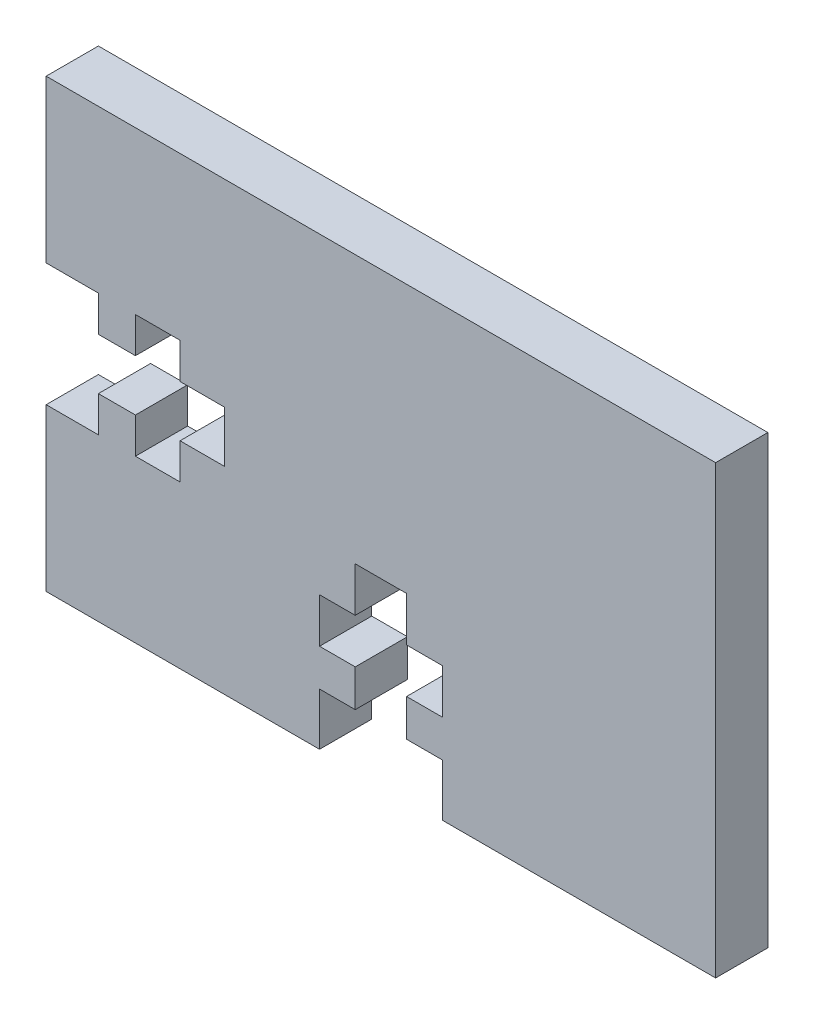
SolidWorks part; units mm, degrees
ref_plane "Front Plane" through (0, 0, 0) normal (0, 0, 1) x (1, 0, 0)
ref_plane "Top Plane" through (0, 0, 0) normal (0, 1, 0) x (1, 0, 0)
ref_plane "Right Plane" through (0, 0, 0) normal (1, 0, 0) x (0, 0, -1)
sketch "Sketch1" plane through (0, 0, 0) normal (0, 0, 1) x (1, 0, 0)
  line L0 (5.08, 14.1605) -> (2.9718, 14.1605)
  line L1 (0, 0) -> (38.1, 0)
  line L2 (0, 0) -> (0, 25.4)
  line L3 (0, 25.4) -> (38.1, 25.4)
  line L4 (38.1, 0) -> (38.1, 25.4)
  line L5 (5.08, 11.2395) -> (5.08, 9.2075)
  line L6 (5.08, 11.2395) -> (2.9718, 11.2395)
  line L7 (5.08, 14.1605) -> (5.08, 16.1925)
  line L8 (5.08, 16.1925) -> (7.62, 16.1925)
  line L9 (7.62, 16.1925) -> (7.62, 14.1605)
  line L10 (7.62, 14.1605) -> (10.16, 14.1605)
  line L11 (0, 12.7) -> (38.1, 12.7) construction
  line L12 (10.16, 14.1605) -> (10.16, 11.2395)
  line L13 (5.08, 9.2075) -> (7.62, 9.2075)
  line L14 (7.62, 9.2075) -> (7.62, 11.2395)
  line L15 (7.62, 11.2395) -> (10.16, 11.2395)
  line L16 (2.9718, 14.1605) -> (2.9718, 16.1925)
  line L17 (2.9718, 16.1925) -> (0, 16.1925)
  line L18 (2.9718, 11.2395) -> (2.9718, 9.2075)
  line L19 (2.9718, 9.2075) -> (0, 9.2075)
  line L20 (19.05, 25.4) -> (19.05, 0) construction
  line L21 (15.5575, 0) -> (15.5575, 2.9718)
  line L22 (15.5575, 2.9718) -> (17.5895, 2.9718)
  line L23 (17.5895, 2.9718) -> (17.5895, 5.08)
  line L24 (17.5895, 5.08) -> (15.5575, 5.08)
  line L25 (15.5575, 5.08) -> (15.5575, 7.62)
  line L26 (15.5575, 7.62) -> (17.5895, 7.62)
  line L27 (17.5895, 7.62) -> (17.5895, 10.16)
  line L28 (17.5895, 10.16) -> (20.5105, 10.16)
  line L29 (22.5425, 0) -> (22.5425, 2.9718)
  line L30 (22.5425, 2.9718) -> (20.5105, 2.9718)
  line L31 (20.5105, 2.9718) -> (20.5105, 5.08)
  line L32 (20.5105, 5.08) -> (22.5425, 5.08)
  line L33 (22.5425, 5.08) -> (22.5425, 7.62)
  line L34 (22.5425, 7.62) -> (20.5105, 7.62)
  line L35 (20.5105, 7.62) -> (20.5105, 10.16)
  point P20 (10.16, 12.7)
  point P43 (19.05, 10.16)
  dimension "D1" = 38.1
  dimension "D2" = 25.4
  dimension "D3" = 3.4925
  dimension "D4" = 10.16
  dimension "D5" = 1.4605
  dimension "D6" = 5.08
  dimension "D7" = 2.54
  dimension "D8" = 2.9718
  dimension "D9" = 1.4605
  dimension "D10" = 10.16
  dimension "D11" = 2.9718
  dimension "D12" = 3.4925
  dimension "D13" = 2.54
  dimension "D14" = 5.08
extrude "Boss-Extrude1" add sketch "Sketch1" along normal blind 2.9718 contours L35 L34 L33 L32 L31 L30 L29 L1 L4 L3 L2 L17 L16 L0 L7 L8 L9 L10 L12 L15 L14 L13 L5 L6 L18 L19 L21 L22 L23 L24 L25 L26 L27 L28 region at (19.9275, 13.1946, 0)
